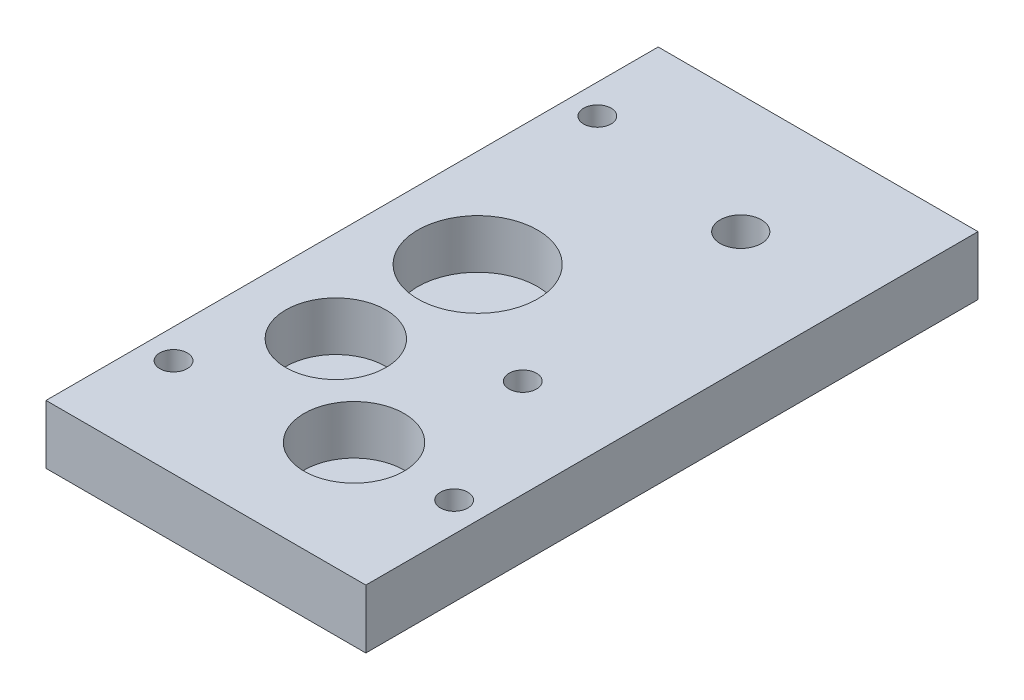
SolidWorks part; units mm, degrees
ref_plane "前视基准面" through (0, 0, 0) normal (0, 0, 1) x (1, 0, 0)
ref_plane "上视基准面" through (0, 0, 0) normal (0, 1, 0) x (1, 0, 0)
ref_plane "右视基准面" through (0, 0, 0) normal (1, 0, 0) x (0, 0, -1)
other "Configuration Table"
sketch "草图1" plane through (0, 0, 0) normal (0, 1, 0) x (1, 0, 0)
  line L1 (-5, 14.2) -> (11.3, 14.2)
  line L2 (-5, 14.2) -> (-5, -17)
  line L3 (-5, -17) -> (11.3, -17)
  line L4 (11.3, 14.2) -> (11.3, -17)
  circle A0 centre (0, 0) radius 3.05
  circle A6 centre (4.7, -11) radius 2.55
  circle A10 centre (-0.3371, -6.8918) radius 2.55
  circle A11 centre (5.2565, 8.1523) radius 1.05
  dimension "D5" = 6.1
  dimension "D6" = 5.1
  dimension "D9" = 5.1
  dimension "D10" = 2.1
  dimension "D1" = 14.2
  dimension "D2" = 5
  dimension "D3" = 11.3
  dimension "D4" = 17
extrude "凸台-拉伸1" add sketch "草图1" along normal blind 3 contours L2 L3 L4 L1
extrude "切除-拉伸1" cut sketch "草图1<3>" against normal blind 2.5 from surface contours A0 | A6 | A10 | A11 starting at face at (3.15, 3, 1.4)
sketch "草图1<3>" plane through (0, 0, 0) normal (0, 1, 0) x (1, 0, 0) same geometry as "草图1"
sketch "草图2" plane through (0, 0, 0) normal (0, -1, 0) x (1, 0, 0)
  circle A0 centre (9.8, 11) radius 1
  circle A1 centre (9.8, 11) radius 0.7
  circle A2 centre (-3.5, 12) radius 1
  circle A3 centre (-3.5, 12) radius 0.7
  circle A4 centre (6.3, 4) radius 1
  circle A5 centre (6.3, 4) radius 0.7
  circle A6 centre (-3.5, -9.6) radius 1
  circle A7 centre (-3.5, -9.6) radius 0.7
  dimension "D1" = 1.4
  dimension "D2" = 2
extrude "切除-拉伸2" cut sketch "草图2" against normal blind 1.5 contours A2 | A0 | A4 | A6
extrude "切除-拉伸3" cut sketch "草图2<3>" against normal through all contours A7 | A1 | A3 | A5
sketch "草图2<3>" plane through (0, 0, 0) normal (0, -1, 0) x (1, 0, 0) same geometry as "草图2"
